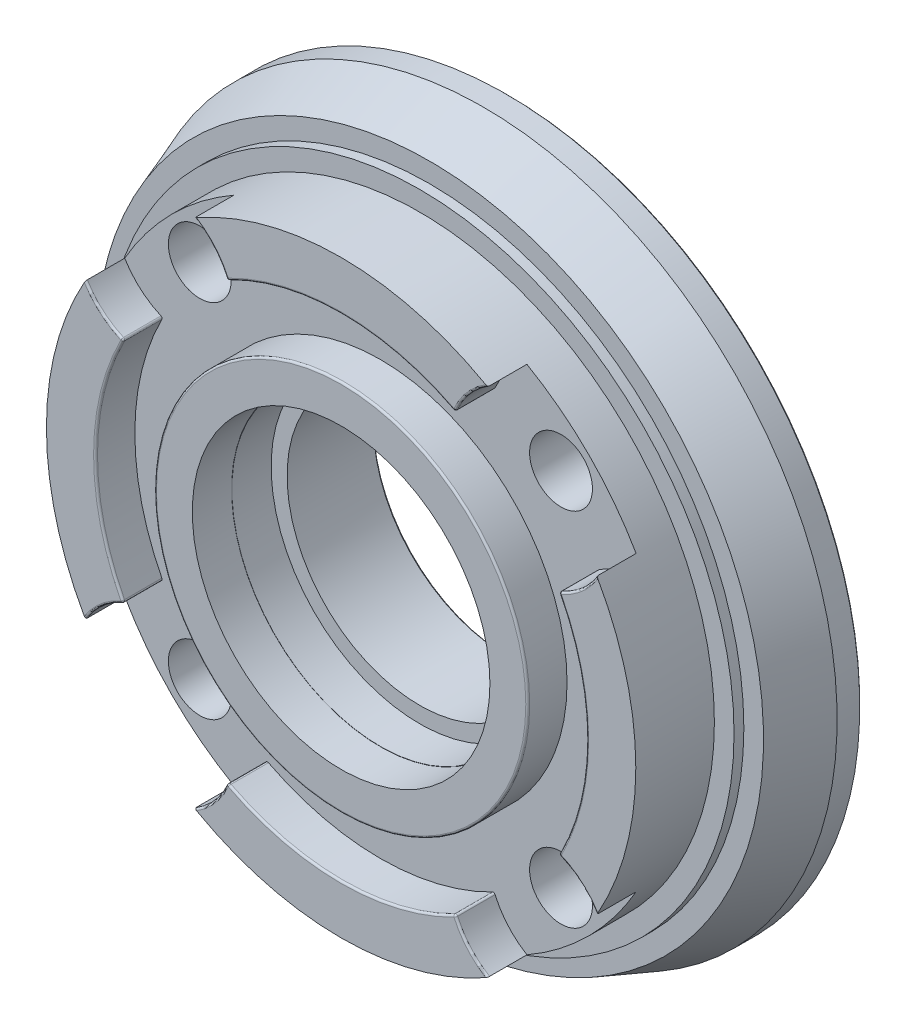
SolidWorks part; units mm, degrees
ref_plane "Front Plane" through (0, 0, 0) normal (0, 0, 1) x (1, 0, 0)
ref_plane "Top Plane" through (0, 0, 0) normal (0, 1, 0) x (1, 0, 0)
ref_plane "Right Plane" through (0, 0, 0) normal (1, 0, 0) x (0, 0, -1)
sketch "Sketch1" plane through (0, 0, 0) normal (0, 0, 1) x (1, 0, 0)
  line L0 (0, 0) -> (13.5, 0) construction
  line L1 (0, 0) -> (9.5459, 9.5459) construction
  circle A0 centre (0, 0) radius 9.5
  circle A1 centre (0, 0) radius 15
  arc A2 (-6.285, 11.9478) -> (-11.9478, 6.285) centre (0, 0) ccw construction
  arc A3 (7.4565, 13.0154) -> (5.7957, 11.0752) centre (9.5459, 9.5459) ccw
  arc A4 (13.0154, -7.4565) -> (11.0752, -5.7957) centre (9.5459, -9.5459) ccw
  arc A5 (-7.4565, -13.0154) -> (-5.7957, -11.0752) centre (-9.5459, -9.5459) ccw
  arc A6 (-13.0154, 7.4565) -> (-11.0752, 5.7957) centre (-9.5459, 9.5459) ccw
  arc A7 (-11.0752, 5.7957) -> (-11.0752, -5.7957) centre (0, 0) ccw
  arc A8 (11.9478, 6.285) -> (6.285, 11.9478) centre (0, 0) ccw construction
  arc A9 (6.285, -11.9478) -> (11.9478, -6.285) centre (0, 0) ccw construction
  arc A10 (-11.9478, -6.285) -> (-6.285, -11.9478) centre (0, 0) ccw construction
  arc A11 (5.7957, 11.0752) -> (-5.7957, 11.0752) centre (0, 0) ccw
  arc A12 (-5.7957, -11.0752) -> (5.7957, -11.0752) centre (0, 0) ccw
  arc A13 (11.0752, -5.7957) -> (11.0752, 5.7957) centre (0, 0) ccw
  arc A14 (-5.7957, 11.0752) -> (-7.4565, 13.0154) centre (-9.5459, 9.5459) ccw
  arc A15 (11.0752, 5.7957) -> (13.0154, 7.4565) centre (9.5459, 9.5459) ccw
  arc A16 (5.7957, -11.0752) -> (7.4565, -13.0154) centre (9.5459, -9.5459) ccw
  arc A17 (-11.0752, -5.7957) -> (-13.0154, -7.4565) centre (-9.5459, -9.5459) ccw
  circle A18 centre (0, 0) radius 7.575
  point P17 (0, 0)
  dimension "D1" = 19
  dimension "D2" = 30
  dimension "D3" = 27
  dimension "D4" = 45
  dimension "D5" = 8.1
  dimension "D6" = 4
  dimension "D7" = 25
  dimension "D8" = 15.15
extrude "Boss-Extrude1" add sketch "Sketch1" along normal blind 2 contours A14 A11 A3 A1 | A15 A13 A4 A1 | A16 A12 A5 A1 | A17 A7 A6 A1 | A0 A18 region at (-9.2313, 0, 0) region at (13.2504, 0, 0) region at (0, 13.2504, 0) region at (0, -13.2504, 0) region at (-13.2504, 0, 0)
sketch "Sketch2" plane through (0, 0, 0) normal (0, 0, 1) x (1, 0, 0)
  circle A0 centre (0, 0) radius 15
extrude "Boss-Extrude2" add sketch "Sketch2" against normal blind 2
fillet "Fillet1" radius 0.1 8 edges at (-5.7957, -11.0752, 1) (5.7957, -11.0752, 1) (11.0752, -5.7957, 1) (11.0752, 5.7957, 1) (5.7957, 11.0752, 1) (-5.7957, 11.0752, 1) (-11.0752, 5.7957, 1) (-11.0752, -5.7957, 1)
fillet "Fillet2" radius 0.1 21 edges at (6.5042, 12.2199, 2) (5.7793, 11.1194, 2) (-6.5042, 12.2199, 2) (-5.7793, 11.1194, 2) (12.2199, -6.5042, 2) (11.1194, -5.7793, 2) (12.2199, 6.5042, 2) (11.1194, 5.7793, 2) (-6.5042, -12.2199, 2) (-5.7793, -11.1194, 2) (6.5042, -12.2199, 2) (5.7793, -11.1194, 2) (-12.2199, 6.5042, 2) (-11.1194, 5.7793, 2) (-12.2199, -6.5042, 2) (-11.1194, -5.7793, 2) (0, 12.5, 2) (12.5, 0, 2) (0, -12.5, 2) (9.5, 0, 2) (-12.5, 0, 2)
sketch "Sketch3" plane through (0, 0, -2) normal (0, 0, -1) x (-1, 0, 0)
  line L1 (9.1924, 9.1924) -> (-9.1924, 9.1924) construction
  line L2 (-9.1924, 9.1924) -> (-9.1924, -9.1924) construction
  line L3 (-9.1924, -9.1924) -> (9.1924, -9.1924) construction
  line L4 (9.1924, -9.1924) -> (9.1924, 9.1924) construction
  circle A0 centre (0, 0) radius 13 construction
  circle A1 centre (-9.1924, 9.1924) radius 1.6
  circle A2 centre (9.1924, 9.1924) radius 1.6
  circle A3 centre (9.1924, -9.1924) radius 1.6
  circle A4 centre (-9.1924, -9.1924) radius 1.6
  point P17 (0, 0)
  dimension "D1" = 26
  dimension "D2" = 3.2
  dimension "D3" = 4
sketch "Sketch4" plane through (0, 0, -2) normal (0, 0, -1) x (-1, 0, 0)
  circle A0 centre (0, 0) radius 16
  dimension "D1" = 32
extrude "Boss-Extrude3" add sketch "Sketch4" along normal blind 0.5
sketch "Sketch5" plane through (0, 0, -2.5) normal (0, 0, -1) x (-1, 0, 0)
  circle A0 centre (0, 0) radius 18
  dimension "D1" = 36
extrude "Boss-Extrude4" add sketch "Sketch5" along normal blind 4
extrude "Cut-Extrude2" cut sketch "Sketch3" against normal through all and the other way through all
sketch "Sketch6" plane through (0, 0, -6.5) normal (0, 0, -1) x (-1, 0, 0)
  circle A0 centre (-9.1924, 9.1924) radius 2.35
  circle A1 centre (9.1924, 9.1924) radius 2.35
  circle A2 centre (9.1924, -9.1924) radius 2.35
  circle A3 centre (-9.1924, -9.1924) radius 2.35
  point P12 (0, 0)
  dimension "D1" = 4.7
  dimension "D2" = 4
extrude "Cut-Extrude3" cut sketch "Sketch6" against normal blind 4
sketch "Sketch7" plane through (0, 0, -6.5) normal (0, 0, -1) x (-1, 0, 0)
  line L0 (0, 0) -> (0, 13) construction
  line L1 (0, 13) -> (-13, 0) construction
  line L2 (-13, 0) -> (0, -13) construction
  line L3 (0, -13) -> (13, 0) construction
  line L4 (13, 0) -> (0, 13) construction
  circle A0 centre (0, 0) radius 13 construction
  circle A1 centre (0, 13) radius 2.35
  circle A2 centre (13, 0) radius 2.35
  circle A3 centre (0, -13) radius 2.35
  circle A4 centre (-13, 0) radius 2.35
  point P17 (0, 0)
  dimension "D1" = 26
  dimension "D2" = 4.7
  dimension "D3" = 4
extrude "Cut-Extrude4" cut sketch "Sketch7" against normal blind 4
sketch "Sketch8" plane through (0, 0, 0) normal (0, 0, 1) x (1, 0, 0)
  circle A0 centre (0, 0) radius 6.75
  dimension "D1" = 13.5
extrude "Middle Cutout" cut sketch "Sketch8" against normal blind 7
chamfer "Chamfer1" distance 0.1 angle 45 2 edges at (-6.75, 0, -6.5) (-18, 0, -6.5)
sketch "Sketch9" plane through (0, 0, 0) normal (0, 0, 1) x (1, 0, 0)
  circle A0 centre (0, 0) radius 7.5625
  dimension "D1" = 15.125
extrude "Cut-Extrude6" cut sketch "Sketch9" against normal blind 2
chamfer "Chamfer2" distance 1 angle 70 1 edges at (-18, 0, -2.5) first distance on face at (-16, 0, -2.5)
